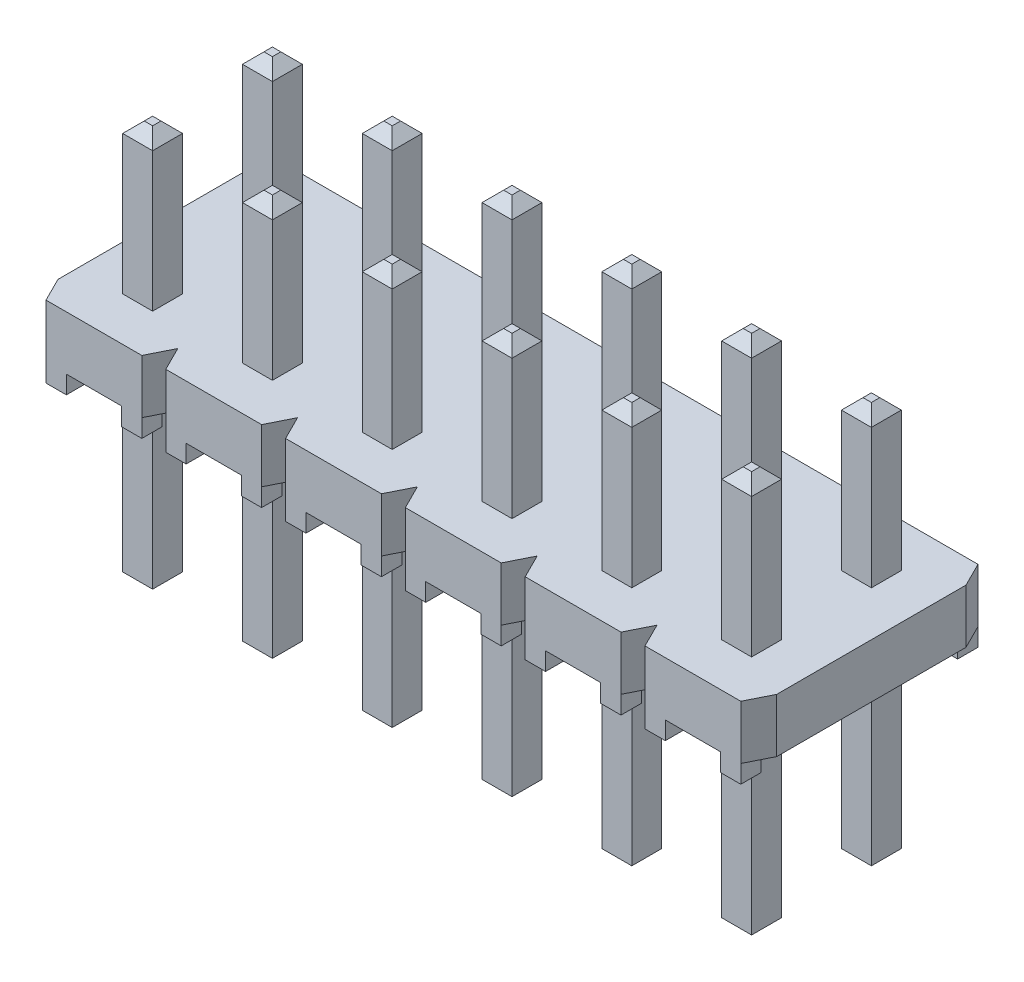
SolidWorks part; units mm, degrees
note: '?' marks a value the reader was unsure of.
ref_plane "Front" through (0, 0, 0) normal (0, 0, 1) x (1, 0, 0)
ref_plane "Top" through (0, 0, 0) normal (0, 1, 0) x (1, 0, 0)
ref_plane "Side" through (0, 0, 0) normal (1, 0, 0) x (0, 0, -1)
sketch "Sketch1" plane through (0, 0, 0) normal (0, 1, 0) x (1, 0, 0)
  line L0 (7.62, -2.5146) -> (-7.62, 2.5146) construction
  line L1 (-7.62, 2.5146) -> (7.62, 2.5146)
  line L2 (-7.62, 2.5146) -> (-7.62, -2.5146)
  line L3 (-7.62, -2.5146) -> (7.62, -2.5146)
  line L4 (7.62, 2.5146) -> (7.62, -2.5146)
  dimension "D1" = 15.24
  dimension "D2" = 5.0292
extrude "Base-Extrude" add sketch "Sketch1" along normal mid plane 1.143
sketch "Sketch3" plane through (0, 0.5715, 0) normal (0, 1, 0) x (-1, 0, 0)
  line L0 (7.5339, 0) -> (10.4044, 0) construction
  line L1 (4.826, 2.5146) -> (5.334, 2.5146)
  line L2 (4.826, -2.5146) -> (5.334, -2.5146)
  line L3 (5.334, 2.5146) -> (5.08, 2.0066)
  line L4 (5.334, -2.5146) -> (5.08, -2.0066)
  line L5 (5.08, 2.0066) -> (4.826, 2.5146)
  line L6 (5.08, -2.0066) -> (4.826, -2.5146)
  line L7 (5.08, 2.5146) -> (5.08, 2.0066) construction
  line L8 (5.08, -2.5146) -> (5.08, -2.0066) construction
  line L9 (7.62, 2.5146) -> (-7.62, 2.5146) construction
  line L11 (6.35, -1.4521) -> (6.35, 2.3817) construction
  line L12 (7.62, -2.0066) -> (7.874, -2.5146)
  line L13 (7.62, 2.0066) -> (7.874, 2.5146)
  line L14 (7.366, -2.5146) -> (7.62, -2.0066)
  line L15 (7.366, 2.5146) -> (7.62, 2.0066)
  line L16 (7.874, -2.5146) -> (7.366, -2.5146)
  line L17 (7.874, 2.5146) -> (7.366, 2.5146)
  line L18 (7.62, -2.5146) -> (7.62, 2.5146) construction
  dimension "D1" = 0.508
  dimension "D2" = 0.508
  dimension "D3" = 1.27
  dimension "D4" = 1.27
extrude "Snap Grooves" cut sketch "Sketch3" against normal through all
sketch "Sketch4" plane through (0, -0.5715, 0) normal (0, -1, 0) x (1, 0, 0)
  line L0 (-6.35, 1.3819) -> (-6.35, -1.499) construction
  line L1 (-7.366, 2.5146) -> (-5.334, 2.5146) construction
  line L2 (-7.366, 2.5146) -> (-6.9342, 2.5146)
  line L3 (-7.366, 2.5146) -> (-7.366, 2.0828)
  line L4 (-7.366, 2.0828) -> (-6.9342, 2.0828)
  line L5 (-6.9342, 2.5146) -> (-6.9342, 2.0828)
  line L6 (-5.7658, 2.5146) -> (-5.7658, 2.0828)
  line L7 (-5.334, 2.0828) -> (-5.7658, 2.0828)
  line L8 (-5.334, 2.5146) -> (-5.334, 2.0828)
  line L9 (-5.334, 2.5146) -> (-5.7658, 2.5146)
  line L11 (-7.62, -2.0066) -> (-7.62, 2.0066) construction
  line L12 (-9.3213, 0) -> (-10.8923, 0) construction
  line L14 (-5.334, -2.5146) -> (-5.7658, -2.5146)
  line L15 (-5.334, -2.5146) -> (-5.334, -2.0828)
  line L16 (-5.334, -2.0828) -> (-5.7658, -2.0828)
  line L17 (-5.7658, -2.5146) -> (-5.7658, -2.0828)
  line L18 (-6.9342, -2.5146) -> (-6.9342, -2.0828)
  line L19 (-7.366, -2.0828) -> (-6.9342, -2.0828)
  line L20 (-7.366, -2.5146) -> (-7.366, -2.0828)
  line L21 (-7.366, -2.5146) -> (-6.9342, -2.5146)
  dimension "D1" = 0.4318
  dimension "D2" = 0.4318
  dimension "D3" = 1.27
extrude "Standoffs" add sketch "Sketch4" along normal blind 0.381
pattern_linear "Position Pattern" count 6 spacing 2.54 along (1, 0, 0) of "Snap Grooves", "Standoffs"
ref_plane "Position 1 Plane" through (-6.35, 0, 0) normal (-1, 0, 0) x (0, 0, 1)
sketch "Sketch5" plane through (-6.35, 0, 0) normal (-1, 0, 0) x (0, 0, 1)
  line L0 (1.27, 3.7465) -> (1.27, -4.7625) construction
  line L1 (0.9525, 3.7465) -> (1.5875, 3.7465)
  line L2 (0.9525, 3.7465) -> (0.9525, -4.7625)
  line L3 (0.9525, -4.7625) -> (1.5875, -4.7625)
  line L4 (1.5875, 3.7465) -> (1.5875, -4.7625)
  line L5 (2.5146, -0.5715) -> (2.5146, 0.5715) construction
  line L6 (-2.0066, 0.5715) -> (2.0066, 0.5715) construction
  dimension "D1" = 1.2446
  dimension "D2" = 0.635
  dimension "D3" = 3.175
  dimension "D4" = 8.509
extrude "Terminal -TH" add sketch "Sketch5" along normal mid plane 0.635
ref_plane "Row 1 Center plane" through (0, 0, 1.27) normal (0, 0, 1) x (1, 0, 0)
chamfer "T1 Tip Bottom" distance 0.2286 angle 45 4 edges at (-6.35, -4.7625, 0.9525) (-6.6675, -4.7625, 1.27) (-6.35, -4.7625, 1.5875) (-6.0325, -4.7625, 1.27)
chamfer "T1 Tip Top" distance 0.2286 angle 45 4 edges at (-6.35, 3.7465, 1.5875) (-6.6675, 3.7465, 1.27) (-6.35, 3.7465, 0.9525) (-6.0325, 3.7465, 1.27)
pattern_linear "Terminal Pattern" count 2 spacing 2.54 along (0, 0, -1) count 6 spacing 2.54 along (1, 0, 0) of "Terminal -TH", "T1 Tip Bottom", "T1 Tip Top"
ref_plane "Center Locking Plane1" through (1.27, 0, 0) normal (-1, 0, 0) x (0, 0, 1)
ref_plane "Initial -S Polarize Plane" through (8.89, 0, 0) normal (1, 0, 0) x (0, 0, -1)
ref_plane "-S Polarize Plane" through (6.35, 0, 0) normal (1, 0, 0) x (0, 0, -1)
ref_plane "Initial -D Polarize Plane" through (-8.89, 0, 0) normal (-1, 0, 0) x (0, 0, 1)
ref_plane "-D Polarize Plane" through (-7.62, 0, 0) normal (-1, 0, 0) x (0, 0, 1)
sketch "Sketch22" plane through (0, 0, 1.27) normal (0, 0, 1) x (1, 0, 0)
  line L0 (0, 2.5876) -> (0, -5.9476) construction
  line L4 (1.27, 0.6286) -> (1.27, -0.6286) construction
  dimension "D1" = 1.27
ref_axis "Axis1" through (0, -5.9476, 1.27) along (0, 1, 0)?
sketch "Sketch23" plane through (1.27, 0, 0) normal (-1, 0, 0) x (0, 0, 1)
  line L0 (0, 1.0124) -> (0, -1.2355) construction
  line L1 (1.27, 3.7465) -> (1.27, -4.7625) construction
  dimension "D1" = 1.27
ref_axis "Axis2" through (1.27, -1.2355, 0) along (0, 1, 0)?
